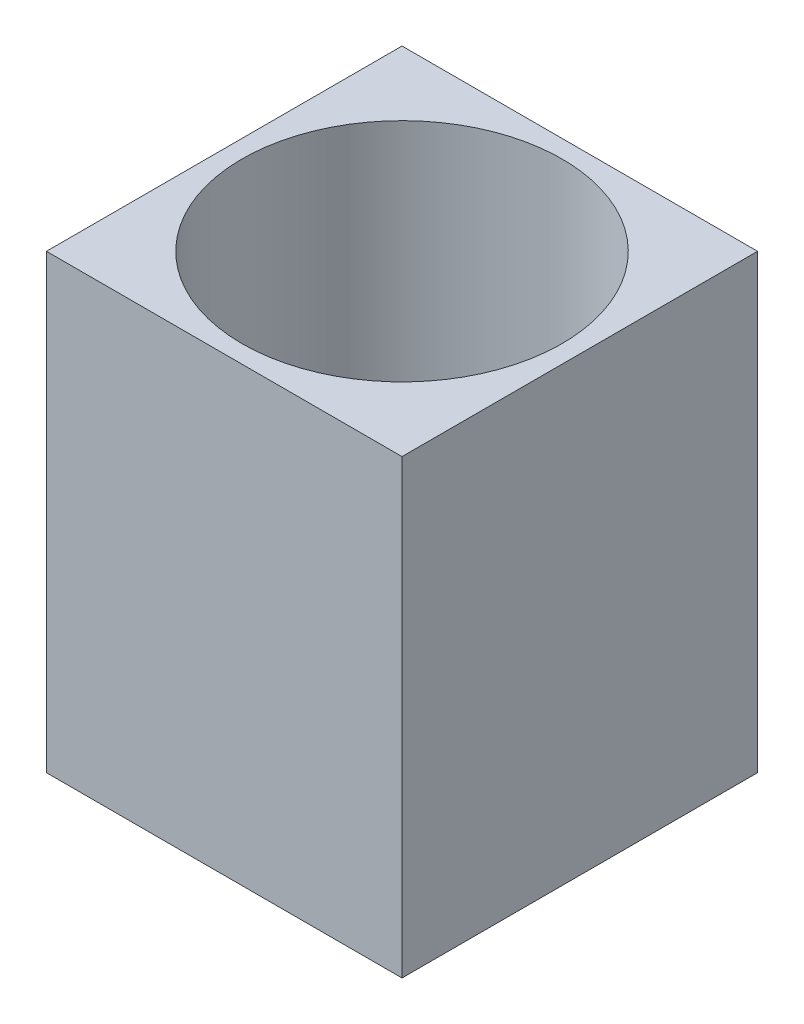
SolidWorks part; units mm, degrees
ref_plane "Front Plane" through (0, 0, 0) normal (0, 0, 1) x (1, 0, 0)
ref_plane "Top Plane" through (0, 0, 0) normal (0, 1, 0) x (1, 0, 0)
ref_plane "Right Plane" through (0, 0, 0) normal (1, 0, 0) x (0, 0, -1)
sketch "Sketch1" plane through (0, 0, 0) normal (0, 1, 0) x (1, 0, 0)
  line L1 (0, 0) -> (10, 0)
  line L2 (0, 0) -> (0, -10)
  line L3 (0, -10) -> (10, -10)
  line L4 (10, 0) -> (10, -10)
  circle A0 centre (5, -5) radius 4.5
  point P4 (0, 0)
  point P8 (5, 0)
  point P9 (0, 0)
  point P10 (0, -5)
  dimension "D3" = 9
  dimension "D1" = 10
  dimension "D2" = 10
extrude "Boss-Extrude1" add sketch "Sketch1" along normal blind 12.7
